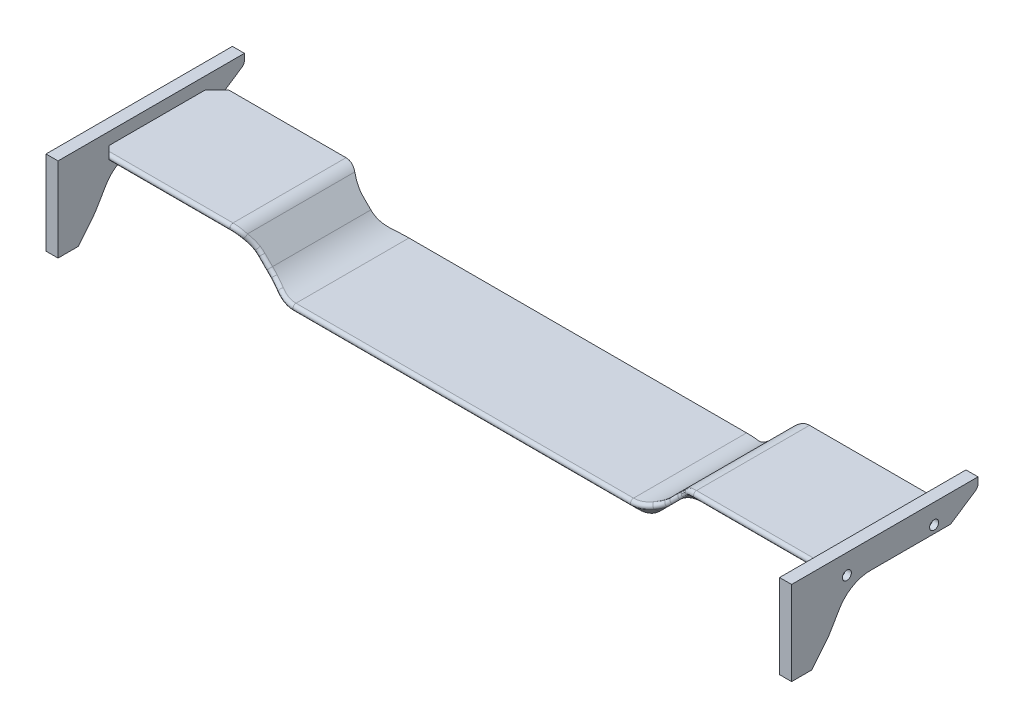
SolidWorks part; units mm, degrees
ref_plane "Plan de face" through (0, 0, 0) normal (0, 0, 1) x (1, 0, 0)
ref_plane "Plan de dessus" through (0, 0, 0) normal (0, 1, 0) x (1, 0, 0)
ref_plane "Plan de droite" through (0, 0, 0) normal (1, 0, 0) x (0, 0, -1)
sketch "Esquisse1" plane through (0, 0, 0) normal (0, 0, 1) x (1, 0, 0)
  line L1 (-600, 150) -> (600, 150)
  line L2 (-600, 150) -> (-600, -150)
  line L3 (-600, -150) -> (600, -150)
  line L4 (600, 150) -> (600, -150)
  line L5 (-600, 150) -> (600, -150) construction
  line L6 (-600, -150) -> (600, 150) construction
  point P0 (0, 0)
  dimension "D1" = 1200
  dimension "D2" = 300
extrude "Boss.-Extru.1" add sketch "Esquisse1" along normal blind 200
sketch "Esquisse2" plane through (0, 0, 200) normal (0, 0, 1) x (1, 0, 0)
  line L0 (-364.7135, 150) -> (-301.4331, 86.7196)
  line L1 (600, 150) -> (-600, 150) construction
  line L2 (-301.4331, 86.7196) -> (301.4331, 86.7196)
  line L3 (-600, 107.8202) -> (-364.7135, 107.8202)
  line L5 (-600, 150) -> (-600, -150) construction
  line L6 (-364.7135, 107.8202) -> (-301.4331, 44.5398)
  line L7 (-301.4331, 44.5398) -> (301.4331, 44.5398)
  line L8 (0, 0) -> (0, -291.5833) construction
  line L9 (364.7135, 107.8202) -> (301.4331, 44.5398)
  line L10 (600, 107.8202) -> (364.7135, 107.8202)
  line L11 (364.7135, 150) -> (301.4331, 86.7196)
  line L12 (-364.7135, 150) -> (-333.0733, 181.6402)
  line L13 (-333.0733, 181.6402) -> (251.9684, 199.4647)
  line L14 (251.9684, 199.4647) -> (364.7135, 150)
  line L15 (600, 107.8202) -> (663.2804, 44.5398)
  line L16 (663.2804, 44.5398) -> (663.2804, 0)
  line L17 (663.2804, 0) -> (554.102, -390.9654)
  line L18 (554.102, -390.9654) -> (-705.9878, -415.3421)
  line L19 (-705.9878, -415.3421) -> (-721.463, -375.4902)
  line L20 (-839.1223, -38.4402) -> (-721.463, -375.4902)
  line L21 (-839.1223, -38.4402) -> (-600, 107.8202)
  point P15 (0, 44.5398)
  point P19 (0, 86.7196)
extrude "Enlèv. mat.-Extru.1" cut sketch "Esquisse2" against normal blind 200
fillet "Congé1" radius 50 8 edges at (364.7135, 150, 100) (364.7135, 107.8202, 100) (-364.7135, 107.8202, 100) (-364.7135, 150, 100) (301.4331, 44.5398, 100) (301.4331, 86.7196, 100) (-301.4331, 44.5398, 100) (-301.4331, 86.7196, 100)
chamfer "Chanfrein1" distance 20 angle 45 20 edges at (600, 128.9101, 200) (492.7121, 107.8202, 200) (366.29, 104.0142, 200) (333.0733, 76.18, 200) (299.8566, 48.3458, 200) (0, 44.5398, 200) (-299.8566, 48.3458, 200) (-333.0733, 76.18, 200) (-366.29, 104.0142, 200) (-492.7121, 107.8202, 200) (-600, 128.9101, 200) (-492.7121, 150, 200) (-366.29, 146.194, 200) (-333.0733, 118.3598, 200) (-299.8566, 90.5256, 200) (0, 86.7196, 200) (299.8566, 90.5256, 200) (333.0733, 118.3598, 200) (366.29, 146.194, 200) (492.7121, 150, 200)
chamfer "Chanfrein2" distance 20 angle 45 20 edges at (299.8566, 90.5256, 0) (0, 86.7196, 0) (-299.8566, 90.5256, 0) (-333.0733, 118.3598, 0) (-366.29, 146.194, 0) (-492.7121, 150, 0) (-600, 128.9101, 0) (-492.7121, 107.8202, 0) (-366.29, 104.0142, 0) (-333.0733, 76.18, 0) (-299.8566, 48.3458, 0) (0, 44.5398, 0) (299.8566, 48.3458, 0) (333.0733, 76.18, 0) (366.29, 104.0142, 0) (492.7121, 107.8202, 0) (600, 128.9101, 0) (492.7121, 150, 0) (366.29, 146.194, 0) (333.0733, 118.3598, 0)
sketch3d "Esquisse3D1"
  line L0 (-600, 150, 180) -> (-385.4242, 150, 180) construction
  line L1 (-350.0688, 135.3553, 180) -> (-316.0777, 101.3642, 180) construction
  line L2 (-280.7224, 86.7196, 180) -> (280.7224, 86.7196, 180) construction
  line L3 (316.0777, 101.3642, 180) -> (350.0688, 135.3553, 180) construction
  line L4 (385.4242, 150, 180) -> (600, 150, 180) construction
  line L5 (-600, 150, 180) -> (-385.4242, 150, 180)
  line L6 (-350.0688, 135.3553, 180) -> (-316.0777, 101.3642, 180)
  line L7 (-280.7224, 86.7196, 180) -> (280.7224, 86.7196, 180)
  line L8 (316.0777, 101.3642, 180) -> (350.0688, 135.3553, 180)
  line L9 (385.4242, 150, 180) -> (600, 150, 180)
  arc A0 (-385.4242, 150, 180) -> (-350.0688, 135.3553, 180) centre (-385.4242, 100, 180) ccw construction
  arc A1 (-316.0777, 101.3642, 180) -> (-280.7224, 86.7196, 180) centre (-280.7224, 136.7196, 180) ccw construction
  arc A2 (280.7224, 86.7196, 180) -> (316.0777, 101.3642, 180) centre (280.7224, 136.7196, 180) ccw construction
  arc A3 (350.0688, 135.3553, 180) -> (385.4242, 150, 180) centre (385.4242, 100, 180) ccw construction
  arc A4 (-385.4242, 150, 180) -> (-350.0688, 135.3553, 180) centre (-385.4242, 100, 180) ccw
  arc A5 (-316.0777, 101.3642, 180) -> (-280.7224, 86.7196, 180) centre (-280.7224, 136.7196, 180) ccw
  arc A6 (280.7224, 86.7196, 180) -> (316.0777, 101.3642, 180) centre (280.7224, 136.7196, 180) ccw
  arc A7 (350.0688, 135.3553, 180) -> (385.4242, 150, 180) centre (385.4242, 100, 180) ccw
  point P5 (-385.4242, 100, 130)
  point P9 (-280.7224, 136.7196, 230)
  point P13 (280.7224, 136.7196, 230)
  point P15 (-385.4242, 100, 130)
  point P17 (385.4242, 100, 130)
  point P19 (-280.7224, 136.7196, 230)
  point P20 (280.7224, 136.7196, 230)
  point P21 (385.4242, 100, 130)
sketch "Esquisse4" plane through (600, 0, 0) normal (1, 0, 0) x (0, 0, -1)
  line L0 (0, 127.8202) -> (-229.7953, 127.8202)
  line L1 (-229.7953, 127.8202) -> (-214.9616, 166.7877)
  line L2 (-214.9616, 166.7877) -> (23.6683, 162.918)
  line L3 (23.6683, 162.918) -> (0, 127.8202)
sweep "Enlèvement de matière-Balayage2" cut profiles "Esquisse4" path "Esquisse3D1"
fillet "Congé2" radius 5 11 edges at (-482.7121, 127.8202, 200) (-372.6037, 124.69, 198.0877) (-351.6855, 105.6051, 188.4952) (-319.8192, 76.0453, 189.2768) (-294.9901, 65.964, 198.0603) (482.7121, 127.8202, 200) (377.2379, 126.5885, 199.2538) (319.8192, 76.0453, 189.2768) (292.1179, 65.445, 198.7532) (0, 64.5398, 200)
sketch "Esquisse5" plane through (600, 0, 0) normal (1, 0, 0) x (0, 0, -1)
  line L0 (-20, 107.8202) -> (-180, 107.8202) construction
  line L1 (0, 102.6334) -> (41.12, 129.7334)
  line L2 (-264.3828, 148.0832) -> (-264.3828, 8.0832)
  line L3 (-264.3828, 8.0832) -> (-230.9596, 8.0832)
  line L4 (45.6172, 148.0832) -> (45.6172, 138.0832)
  line L5 (-100, 107.8202) -> (-90.4575, 102.6334) construction
  line L6 (-109.5425, 102.6334) -> (-100, 107.8202) construction
  line L7 (45.6172, 148.0832) -> (-264.3828, 148.0832)
  line L8 (-202.6845, 42.9354) -> (-230.9596, 8.0832)
  line L10 (-202.6845, 42.9354) -> (-184.7198, 73.2341)
  line L11 (-133.1097, 102.6334) -> (0, 102.6334)
  arc A0 (-184.7198, 73.2341) -> (-133.1097, 102.6334) centre (-133.1097, 42.6334) cw
  arc A1 (41.12, 129.7334) -> (45.6172, 138.0832) centre (35.6172, 138.0832) ccw
  point P0 (-100, 107.8202)
  dimension "D1" = 60
  dimension "D2" = 10
  dimension "D3" = 140
  dimension "D4" = 310
  dimension "D5" = 10
extrude "Boss.-Extru.2" add sketch "Esquisse5" along normal blind 20
mirror "Symétrie1" about plane through (0, 0, 0) normal (1, 0, 0) of "Boss.-Extru.2"
sketch "Esquisse6" plane through (620, 0, 0) normal (1, 0, 0) x (0, 0, -1)
  circle A0 centre (-172.4214, 115.3221) radius 7.502
  circle A1 centre (-27.3597, 115.3221) radius 7.502
extrude "Enlèv. mat.-Extru.2" cut sketch "Esquisse6" against normal blind 10
sketch "Esquisse7" plane through (-620, 0, 0) normal (-1, 0, 0) x (0, 0, 1)
  circle A0 centre (27.3597, 115.3221) radius 7.502
  circle A1 centre (172.4214, 115.3221) radius 7.502
extrude "Enlèv. mat.-Extru.3" cut sketch "Esquisse7" against normal blind 10
scale "Scale1" scale about centroid uniform scaling yes scale factor 2
